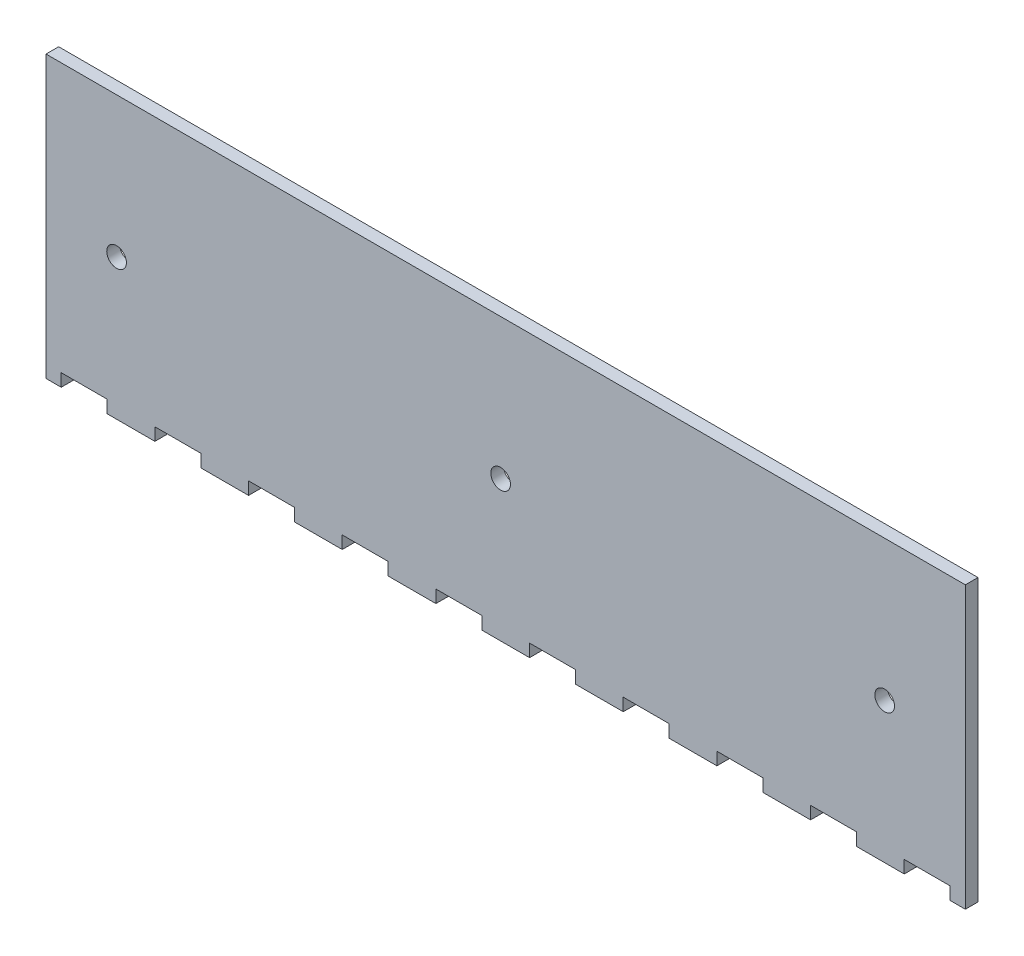
SolidWorks part; units mm, degrees
ref_plane "Plan de face" through (0, 0, 0) normal (0, 0, 1) x (1, 0, 0)
ref_plane "Plan de dessus" through (0, 0, 0) normal (0, 1, 0) x (1, 0, 0)
ref_plane "Plan de droite" through (0, 0, 0) normal (1, 0, 0) x (0, 0, -1)
sketch "Esquisse1" plane through (0, 0, 0) normal (0, 0, 1) x (1, 0, 0)
  line L1 (98.15, 0) -> (-98.15, 0)
  line L2 (98.15, 0) -> (98.15, -60)
  line L3 (98.15, -60) -> (-98.15, -60)
  line L4 (-98.15, 0) -> (-98.15, -60)
  dimension "D1" = 196.3
  dimension "D2" = 60
extrude "Boss.-Extru.1" add sketch "Esquisse1" along normal blind 2.7
sketch "Esquisse3" plane through (0, 0, 0) normal (0, 0, 1) x (1, 0, 0)
  line L0 (-98.15, -60) -> (98.15, -60) construction
  line L1 (5.1, -60) -> (14.9, -60)
  line L2 (5.1, -60) -> (5.1, -57.3)
  line L3 (5.1, -57.3) -> (14.9, -57.3)
  line L4 (14.9, -60) -> (14.9, -57.3)
  line L5 (10, -57.3) -> (10, -60) construction
  line L6 (0, 0) -> (0, -60) construction
  dimension "D1" = 9.8
  dimension "D2" = 2.7
  dimension "D3" = 10
extrude "Enlèv. mat.-Extru.1" cut sketch "Esquisse3" along normal blind 2.7
pattern_linear "Répétition linéaire2" count 5 spacing 20 along (1, 0, 0) count 6 spacing 20 along (-1, 0, 0) of "Enlèv. mat.-Extru.1" pattern seed only yes
sketch "Esquisse2" plane through (0, 0, 0) normal (0, 0, 1) x (1, 0, 0)
  line L0 (-98.15, 0) -> (-98.15, -60) construction
  line L1 (-98.15, -4.75) -> (-100.85, -4.75)
  line L2 (-98.15, -4.75) -> (-98.15, -14.25)
  line L3 (-98.15, -14.25) -> (-100.85, -14.25)
  line L4 (-100.85, -4.75) -> (-100.85, -14.25)
  line L5 (-100.85, -9.5) -> (-98.15, -9.5) construction
  line L6 (98.15, 0) -> (-98.15, 0) construction
  dimension "D1" = 9.5
  dimension "D2" = 9.5
  dimension "D3" = 2.7
extrude "Boss.-Extru.2" [suppressed] add sketch "Esquisse2" along normal blind 2.7
mirror "Symétrie1" [suppressed] about plane through (0, 0, 0) normal (1, 0, 0)
pattern_linear "Répétition linéaire1" [suppressed] count 3 spacing 19 of bodies 104
sketch "Esquisse4" [suppressed] plane through (0, 0, 0) normal (0, 0, 1) x (1, 0, 0)
  line L0 (10, 0) -> (10, -4.85) construction
  line L1 (8.65, -4.85) -> (11.35, -4.85)
  line L2 (8.65, -4.85) -> (8.65, -14.15)
  line L3 (8.65, -14.15) -> (11.35, -14.15)
  line L4 (11.35, -4.85) -> (11.35, -14.15)
  line L5 (8.65, -9.5) -> (11.35, -9.5) construction
  line L6 (98.15, 0) -> (-98.15, 0) construction
  dimension "D1" = 9.5
  dimension "D2" = 9.3
  dimension "D3" = 2.7
  dimension "D4" = 10
extrude "Enlèv. mat.-Extru.2" [suppressed] cut sketch "Esquisse4" along normal through all
pattern_linear "Répétition linéaire3" [suppressed] count 3 spacing 19 of bodies 107
sketch "Esquisse5" plane through (0, 0, 0) normal (0, 0, 1) x (1, 0, 0)
  line L2 (-100.85, -30) -> (98.15, -30) construction
  line L3 (98.15, -60) -> (98.15, 0) construction
  circle A0 centre (-83.081, -30) radius 2.1
  circle A1 centre (-1.081, -30) radius 2.1
  circle A2 centre (80.919, -30) radius 2.1
  point P0 (98.15, -30)
  dimension "D1" = 4.2
  dimension "D2" = 30
  dimension "D3" = 17.231
  dimension "D4" = 82
  dimension "D5" = 82
extrude "Enlèv. mat.-Extru.3" cut sketch "Esquisse5" along normal blind 10
ref_axis "Axe1" [suppressed] through (-83.081, -30, 28.1458) along (0, 0, -1)
ref_axis "Axe2" [suppressed] through (-1.081, -30, 22.4012) along (0, 0, -1)
ref_axis "Axe3" [suppressed] through (80.919, -30, 25.3776) along (0, 0, -1)
